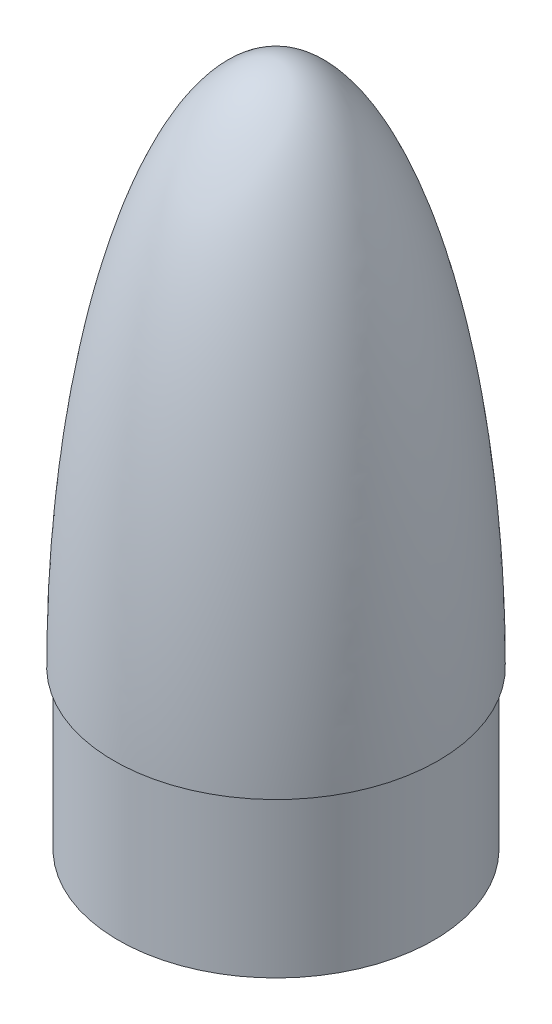
SolidWorks part; units mm, degrees
material "ABS"
ref_plane "Front Plane" through (0, 0, 0) normal (0, 0, 1) x (1, 0, 0)
ref_plane "Top Plane" through (0, 0, 0) normal (0, 1, 0) x (1, 0, 0)
ref_plane "Right Plane" through (0, 0, 0) normal (1, 0, 0) x (0, 0, -1)
sketch "Sketch1" plane through (0, 0, 0) normal (0, 0, 1) x (1, 0, 0)
  line L0 (0, 254) -> (0, 0) construction
  line L1 (78.359, 0) -> (0, 0)
  line L2 (0, 0) -> (0, 254)
  spline S0 degree 4 poles (77.9662, -25.3999) (78.0154, -23.8095) (78.1056, -20.6522) (78.1976, -16.6458) (78.2773, -11.9379) (78.3233, -7.8867) (78.3478, -4.9036) (78.3593, -1.4843) (78.3601, 0.7911) (78.3527, 3.5863) (78.3388, 5.9889) (78.318, 8.3522) (78.2903, 10.7456) (78.247, 13.7314) (78.1811, 17.3117) (78.0839, 21.4904) (77.9448, 26.2641) (77.7777, 31.0376) (77.5823, 35.8096) (77.3585, 40.5805) (77.0429, 46.5423) (76.6791, 52.5014) (76.2664, 58.4574) (75.8041, 64.4096) (75.404, 69.1689) (74.8656, 75.1148) (74.1574, 82.244) (73.2383, 90.5517) (72.0557, 100.0308) (70.7355, 109.4917) (69.2709, 118.9313) (67.25, 130.6999) (64.5017, 144.7638) (61.3086, 158.736) (57.591, 172.5772) (53.383, 186.2759) (49.2387, 198.0448) (44.4832, 209.5873) (38.9429, 220.7192) (34.2562, 228.6936) (29.8187, 235.0954) (25.6242, 240.1829) (21.9789, 243.9262) (18.5702, 246.8595) (15.4743, 249.0762) (12.5634, 250.7857) (9.7723, 252.0835) (7.0631, 253.0286) (4.2754, 253.6868) (2.188, 253.9399) (0.7672, 253.9999) (0, 254) knots 0 0 0 0 0 0.020823 0.041645 0.052056 0.062468 0.072879 0.08329 0.09112 0.098949 0.106779 0.114608 0.122438 0.130267 0.145926 0.161585 0.177244 0.192903 0.208562 0.224221 0.23988 0.271198 0.286857 0.302516 0.318175 0.333834 0.365152 0.39647 0.427788 0.459106 0.490424 0.521742 0.584379 0.647015 0.678333 0.709651 0.772287 0.810589 0.841907 0.872608 0.893486 0.912628 0.928287 0.941045 0.952387 0.962498 0.972496 0.981349 0.98995 1 1 1 1 1 construction
  spline S1 degree 4 poles (78.359, 0) (78.359, 0.5473) (78.3578, 1.6496) (78.3527, 3.5863) (78.3388, 5.9889) (78.318, 8.3522) (78.2903, 10.7456) (78.247, 13.7314) (78.1811, 17.3117) (78.0839, 21.4904) (77.9448, 26.2641) (77.7777, 31.0376) (77.5823, 35.8096) (77.3585, 40.5805) (77.0429, 46.5423) (76.6791, 52.5014) (76.2664, 58.4574) (75.8041, 64.4096) (75.404, 69.1689) (74.8656, 75.1148) (74.1574, 82.244) (73.2383, 90.5517) (72.0557, 100.0308) (70.7355, 109.4917) (69.2709, 118.9313) (67.25, 130.6999) (64.5017, 144.7638) (61.3086, 158.736) (57.591, 172.5772) (53.383, 186.2759) (49.2387, 198.0448) (44.4832, 209.5873) (38.9429, 220.7192) (34.2562, 228.6936) (29.8187, 235.0954) (25.6242, 240.1829) (21.9789, 243.9262) (18.5702, 246.8595) (15.4743, 249.0762) (12.5634, 250.7857) (9.7723, 252.0835) (7.0631, 253.0286) (4.2754, 253.6868) (2.188, 253.9399) (0.7672, 253.9999) (0, 254) knots 0.08329 0.08329 0.08329 0.08329 0.08329 0.09112 0.098949 0.106779 0.114608 0.122438 0.130267 0.145926 0.161585 0.177244 0.192903 0.208562 0.224221 0.23988 0.271198 0.286857 0.302516 0.318175 0.333834 0.365152 0.39647 0.427788 0.459106 0.490424 0.521742 0.584379 0.647015 0.678333 0.709651 0.772287 0.810589 0.841907 0.872608 0.893486 0.912628 0.928287 0.941045 0.952387 0.962498 0.972496 0.981349 0.98995 1 1 1 1 1
revolve "Revolve1" add sketch "Sketch1" angle 360 about L0
sketch "Sketch2" plane through (0, 0, 0) normal (0, -1, 0) x (1, 0, 0)
  circle A0 centre (0, 0) radius 76.2
extrude "Boss-Extrude1" add sketch "Sketch2" along normal blind 76.2
ref_axis "Axis1" through (0, 270.51, 0) along (0, -1, 0)
sketch "Sketch4" plane through (0, 0, 0) normal (0, 1, 0) x (1, 0, 0)
  line L0 (76.2, 0) -> (-78.359, 0) construction
  line L1 (0, -78.359) -> (0, 90.3851) construction
  circle A0 centre (0, 0) radius 76.2 construction
  circle A1 centre (0, 0) radius 78.359 construction
  circle A2 centre (48.26, 0) radius 17.78
  circle A3 centre (0, -48.26) radius 17.78
  circle A4 centre (-48.26, 0) radius 17.78
  circle A5 centre (0, 48.26) radius 17.78
  point P20 (0, 0)
  point P43 (0, 0.8087)
  dimension "D2" = 35.56
  dimension "D1" = 48.26
  dimension "D3" = 4
extrude "Cut-Extrude1" cut sketch "Sketch4" along normal blind 96.52
sketch "Sketch5" plane through (0, 0, 0) normal (0, 1, 0) x (1, 0, 0)
  line L0 (-83.8326, 0) -> (109.4642, 0) construction
  line L1 (0, 82.5318) -> (0, -82.1463) construction
  circle A0 centre (20.32, 0) radius 8.255
  circle A1 centre (10.16, -17.5976) radius 8.255
  circle A2 centre (-10.16, -17.5976) radius 8.255
  circle A3 centre (-20.32, 0) radius 8.255
  circle A4 centre (-10.16, 17.5976) radius 8.255
  circle A5 centre (10.16, 17.5976) radius 8.255
  point P20 (0, 0)
  dimension "D2" = 16.51
  dimension "D1" = 20.32
  dimension "D3" = 6
extrude "Cut-Extrude2" cut sketch "Sketch5" along normal blind 119.38 from offset 106.68
sketch "Sketch6" plane through (0, 0, 0) normal (0, 0, 1) x (1, 0, 0)
  line L0 (-30.48, 96.52) -> (-48.26, 117.7094)
  line L1 (-48.26, 96.52) -> (-48.26, 0) construction
  line L2 (-66.04, 96.52) -> (-30.48, 96.52) construction
  line L3 (-48.26, 117.7094) -> (-48.26, 96.52)
  line L4 (-48.26, 96.52) -> (-30.48, 96.52)
  dimension "D1" = 50
revolve "Cut-Revolve2" [suppressed] cut sketch "Sketch6" angle 360
sketch "Sketch7" [suppressed] plane through (0, 0, 0) normal (0, 0, 1) x (1, 0, 0)
  line L0 (17.78, 96.52) -> (0, 117.7094)
  line L1 (0, 270.51) -> (0, -92.71) construction
  line L2 (-17.78, 96.52) -> (17.78, 96.52) construction
  line L3 (0, 117.7094) -> (0, 96.52)
  line L4 (0, 96.52) -> (17.78, 96.52)
  dimension "D1" = 50
ref_plane "Plane1" [suppressed] through (0, 0, 48.26) normal (0, 0, 1) x (1, 0, 0)
sketch "Sketch8" [suppressed] plane through (0, 0, 48.26) normal (0, 0, 1) x (1, 0, 0)
  line L0 (0, 96.52) -> (17.78, 96.52)
  line L1 (17.78, 96.52) -> (0, 117.7094)
  line L2 (0, 117.7094) -> (0, 96.52)
revolve "Cut-Revolve4" [suppressed] cut sketch "Sketch8" angle 360
sketch "Sketch9" plane through (0, 0, 0) normal (0, 0, 1) x (1, 0, 0)
  line L0 (48.26, 96.52) -> (66.04, 96.52)
  line L1 (30.48, 96.52) -> (66.04, 96.52) construction
  line L2 (66.04, 96.52) -> (48.26, 117.7094)
  line L3 (48.26, 96.52) -> (48.26, 0) construction
  line L4 (48.26, 117.7094) -> (48.26, 96.52)
  dimension "D1" = 50
revolve "Cut-Revolve5" [suppressed] cut sketch "Sketch9" angle 360
ref_plane "Plane2" through (0, 0, -48.26) normal (0, 0, 1) x (1, 0, 0)
sketch "Sketch11" [suppressed] plane through (0, 0, -48.26) normal (0, 0, 1) x (1, 0, 0)
  line L0 (0, 96.52) -> (17.78, 96.52)
  line L1 (17.78, 96.52) -> (-17.78, 96.52) construction
  line L2 (17.78, 96.52) -> (0, 117.7094)
  line L3 (0, 117.7094) -> (0, 96.52)
revolve "Cut-Revolve6" [suppressed] cut sketch "Sketch11" angle 360
sketch "Sketch12" plane through (0, 0, 0) normal (0, 0, 1) x (1, 0, 0)
  line L0 (-20.32, 226.06) -> (-12.065, 226.06)
  line L1 (-28.575, 226.06) -> (-12.065, 226.06) construction
  line L2 (-12.065, 226.06) -> (-20.32, 235.8979)
  line L3 (-20.32, 226.06) -> (-20.32, 106.68) construction
  line L4 (-20.32, 235.8979) -> (-20.32, 226.06)
  dimension "D1" = 50
revolve "Cut-Revolve7" [suppressed] cut sketch "Sketch12" angle 360
sketch "Sketch14" plane through (0, 0, 0) normal (0, 0, 1) x (1, 0, 0)
  line L0 (20.32, 226.06) -> (28.575, 226.06)
  line L1 (12.065, 226.06) -> (28.575, 226.06) construction
  line L2 (28.575, 226.06) -> (20.32, 235.8979)
  line L3 (20.32, 226.06) -> (20.32, 106.68) construction
  line L4 (20.32, 235.8979) -> (20.32, 226.06)
  dimension "D1" = 50
revolve "Cut-Revolve8" [suppressed] cut sketch "Sketch14" angle 360 about L4
ref_plane "Plane3" [suppressed] through (0, 0, 17.5976) normal (0, 0, 1) x (1, 0, 0)
sketch "Sketch15" [suppressed] plane through (0, 0, 17.5976) normal (0, 0, 1) x (1, 0, 0)
  line L0 (-10.16, 226.06) -> (-1.905, 226.06)
  line L1 (-18.415, 226.06) -> (-1.905, 226.06) construction
  line L2 (-1.905, 226.06) -> (-10.16, 235.8979)
  line L3 (-10.16, 226.06) -> (-10.16, 106.68) construction
  line L4 (-10.16, 235.8979) -> (-10.16, 226.06)
  dimension "D1" = 50
revolve "Cut-Revolve9" [suppressed] cut sketch "Sketch15" angle 360
sketch "Sketch16" [suppressed] plane through (0, 0, 17.5976) normal (0, 0, 1) x (1, 0, 0)
  line L0 (10.16, 226.06) -> (18.415, 226.06)
  line L1 (1.905, 226.06) -> (18.415, 226.06) construction
  line L2 (18.415, 226.06) -> (10.16, 235.8979)
  line L3 (10.16, 226.06) -> (10.16, 106.68) construction
  line L4 (10.16, 235.8979) -> (10.16, 226.06)
  dimension "D1" = 50
revolve "Cut-Revolve10" [suppressed] cut sketch "Sketch16" angle 360 about L4
ref_plane "Plane4" [suppressed] through (0, 0, -17.5976) normal (0, 0, 1) x (1, 0, 0)
sketch "Sketch17" [suppressed] plane through (0, 0, -17.5976) normal (0, 0, 1) x (1, 0, 0)
  line L0 (10.16, 226.06) -> (18.415, 226.06)
  line L1 (18.415, 226.06) -> (1.905, 226.06) construction
  line L2 (18.415, 226.06) -> (10.16, 235.8979)
  line L3 (10.16, 235.8979) -> (10.16, 226.06)
revolve "Cut-Revolve11" [suppressed] cut sketch "Sketch17" angle 360 about L3
sketch "Sketch18" [suppressed] plane through (0, 0, -17.5976) normal (0, 0, 1) x (1, 0, 0)
  line L0 (-10.16, 226.06) -> (-1.905, 226.06)
  line L1 (-1.905, 226.06) -> (-18.415, 226.06) construction
  line L2 (-1.905, 226.06) -> (-10.16, 235.8979)
  line L3 (-10.16, 235.8979) -> (-10.16, 226.06)
revolve "Cut-Revolve12" [suppressed] cut sketch "Sketch18" angle 360 about L3
sketch "Sketch19" plane through (0, 0, 0) normal (0, 1, 0) x (1, 0, 0)
  circle A0 centre (0, 0) radius 15.24
  dimension "D1" = 30.48
extrude "Cut-Extrude3" cut sketch "Sketch19" along normal blind 101.6 from offset 25.4 offset against normal yes
sketch "Sketch20" plane through (0, 0, 0) normal (0, 0, 1) x (1, 0, 0)
  line L5 (0, 76.2) -> (15.24, 76.2)
  line L6 (-15.24, 76.2) -> (15.24, 76.2) construction
  line L7 (15.24, 76.2) -> (0, 94.3623)
  line L8 (0, 270.51) -> (0, -92.71) construction
  line L9 (0, 94.3623) -> (0, 76.2)
  dimension "D1" = 50
revolve "Cut-Revolve13" [suppressed] cut sketch "Sketch20" angle 360 about axis through (0, 270.51, 0) along (0, -1, 0)
sketch "Sketch21" plane through (0, -76.2, 0) normal (0, -1, 0) x (1, 0, 0)
  line L1 (-25.4, 25.4) -> (25.4, 25.4) construction
  line L2 (-25.4, 25.4) -> (-25.4, -25.4) construction
  line L3 (-25.4, -25.4) -> (25.4, -25.4) construction
  line L4 (25.4, 25.4) -> (25.4, -25.4) construction
  circle A0 centre (-37.813, 0) radius 2.6035
  circle A1 centre (0, 37.813) radius 2.6035
  circle A2 centre (37.813, 0) radius 2.6035
  circle A3 centre (0, -37.813) radius 2.6035
  point P12 (-25.4, 0)
  point P14 (25.4, 0)
  point P15 (0, 25.4)
  dimension "D1" = 50.8
  dimension "D3" = 5.207
  dimension "D5" = 12.413
  dimension "D8" = 5.207
  dimension "D9" = 5.207
  dimension "D10" = 5.207
  dimension "D2" = 50.8
  dimension "D4" = 12.413
  dimension "D6" = 12.413
  dimension "D7" = 12.413
extrude "Cut-Extrude4" cut sketch "Sketch21" against normal blind 9.525
sketch "Sketch22" plane through (0, -76.2, 0) normal (0, -1, 0) x (1, 0, 0)
  line L0 (-71.842, 0) -> (0, 71.842) construction
  line L1 (0, 71.842) -> (71.842, 0) construction
  line L2 (71.842, 0) -> (0, -71.842) construction
  line L3 (0, -71.842) -> (-71.842, 0) construction
  line L4 (0, -37.813) -> (37.813, 0) construction
  circle A0 centre (-35.921, -35.921) radius 2.6035
  circle A1 centre (-35.921, 35.921) radius 2.6035
  circle A2 centre (35.921, 35.921) radius 2.6035
  circle A3 centre (35.921, -35.921) radius 2.6035
  dimension "D6" = 5.207
  dimension "D7" = 5.207
  dimension "D8" = 5.207
  dimension "D9" = 5.207
  dimension "D1" = 101.6
  dimension "D2" = 101.6
  dimension "D3" = 50.8
  dimension "D4" = 50.8
  dimension "D5" = 90
extrude "Cut-Extrude5" cut sketch "Sketch22" against normal blind 9.525
sketch "Sketch3" plane through (0, 0, 0) normal (0, 0, 1) x (1, 0, 0)
  line L0 (0, 0) -> (50.6956, 0)
  line L1 (-76.2, 0) -> (76.2, 0) construction
  line L2 (0, 0) -> (0, 122.511)
  line L3 (0, 270.51) -> (0, -92.71) construction
  arc A0 (50.6956, 0) -> (0, 122.511) centre (-122.6821, 0) ccw
revolve "Cut-Revolve1" [suppressed] cut sketch "Sketch3" angle 360 about axis through (0, 270.51, 0) along (0, -1, 0)
equation "\"Bodytube_OD\"= 6.17in"
equation "\"Bodytube_ID\"= 5.998in"
equation "\"R\"= \"Bodytube_ID\" / 2"
equation "\"L\"= 30in"
